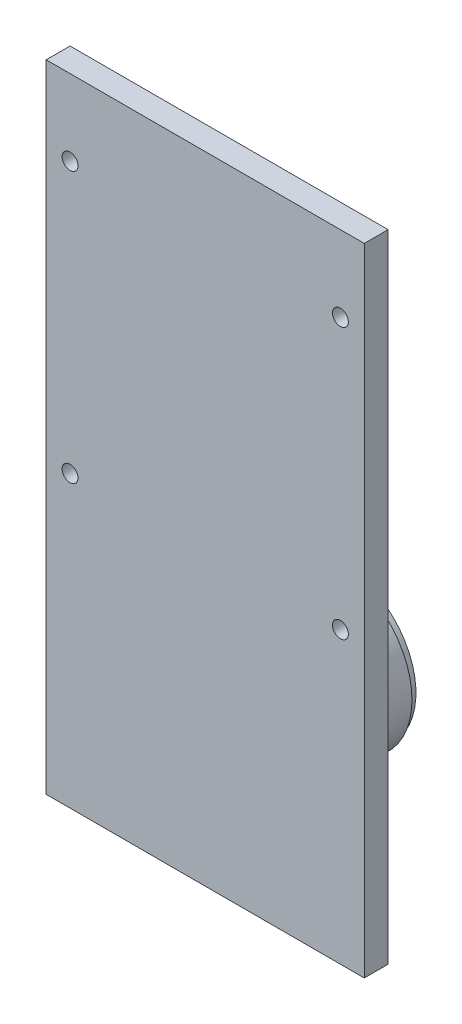
SolidWorks part; units mm, degrees
ref_plane "Front Plane" through (0, 0, 0) normal (0, 0, 1) x (1, 0, 0)
ref_plane "Top Plane" through (0, 0, 0) normal (0, 1, 0) x (1, 0, 0)
ref_plane "Right Plane" through (0, 0, 0) normal (1, 0, 0) x (0, 0, -1)
sketch "Sketch1" plane through (0, 0, 0) normal (0, 0, 1) x (1, 0, 0)
  line L1 (0, 0) -> (40, 0)
  line L2 (0, 0) -> (0, 80)
  line L3 (0, 80) -> (40, 80)
  line L4 (40, 0) -> (40, 80)
  dimension "D1" = 40
  dimension "D2" = 80
extrude "Boss-Extrude1" add sketch "Sketch1" along normal blind 3
sketch "Sketch2" plane through (0, 0, 3) normal (0, 0, 1) x (1, 0, 0)
  line L4 (0, 80) -> (0, 0) construction
  line L5 (40, 0) -> (40, 80) construction
  circle A0 centre (3, 70.4461) radius 1
  circle A1 centre (3, 36.4461) radius 1
  circle A2 centre (37, 70.4461) radius 1
  circle A3 centre (37, 36.4461) radius 1
  dimension "D1" = 2
  dimension "D4" = 2
  dimension "D9" = 2
  dimension "D10" = 2
  dimension "D2" = 3
  dimension "D3" = 3
  dimension "D5" = 3
  dimension "D6" = 3
extrude "Cut-Extrude1" cut sketch "Sketch2" against normal up to surface (3 mm away) up to face at (20, 40, 0)
sketch "Sketch3" plane through (0, 0, 0) normal (0, 0, -1) x (-1, 0, 0)
  line L0 (0, 80) -> (0, 0) construction
  circle A0 centre (-20, 17.3035) radius 15
  dimension "D1" = 30
  dimension "D2" = 20
extrude "Boss-Extrude2" add sketch "Sketch3" along normal blind 3 contours A0
fillet "Fillet1" radius 1.2 1 edges at (5, 17.3035, 0)
sketch "Sketch4" plane through (0, 0, -3) normal (0, 0, -1) x (-1, 0, 0)
  circle A0 centre (-20, 17.3035) radius 10
  dimension "D1" = 20
extrude "Boss-Extrude3" add sketch "Sketch4" along normal blind 10 contours A0
ref_plane "Plane1" through (0, 0, -13) normal (0, 0, -1) x (-1, 0, 0)
sketch "Sketch10" plane through (0, 0, -13) normal (0, 0, -1) x (-1, 0, 0)
  line L1 (-20, 25.8371) -> (-20, 8.7699)
  arc A0 (-20, 8.7699) -> (-20, 25.8371) centre (-20, 17.3035) ccw
revolve "Cut-Revolve2" cut sketch "Sketch10" angle 360 about L1
sketch "Sketch13" plane through (0, 0, -13) normal (0, 0, -1) x (-1, 0, 0)
sketch "Sketch14" plane through (0, 0, -13) normal (0, 0, -1) x (-1, 0, 0)
  circle A0 centre (-20, 17.3035) radius 9.5
extrude "Boss-Extrude4" add sketch "Sketch14" along normal blind 1
sketch "Sketch15" plane through (0, 0, -14) normal (0, 0, -1) x (-1, 0, 0)
  circle A0 centre (-20, 17.3035) radius 7.5
extrude "Cut-Extrude7" cut sketch "Sketch15" against normal blind 1
